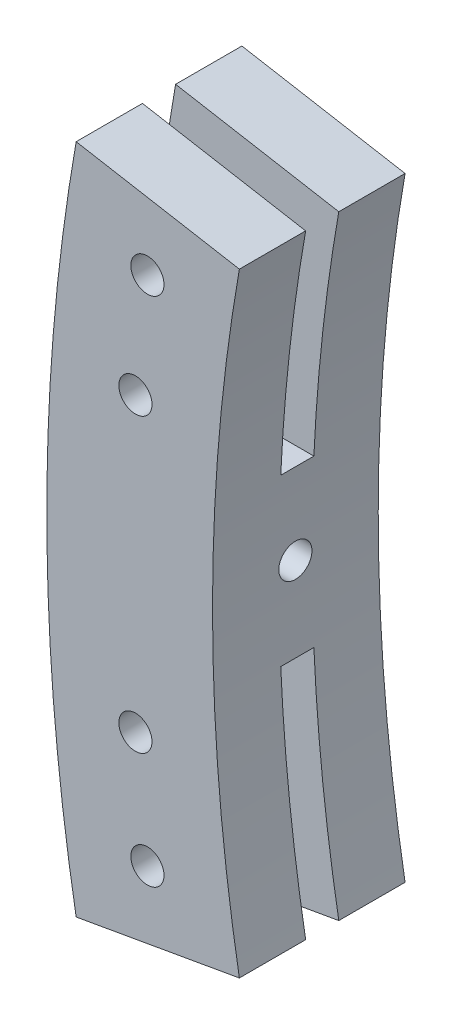
SolidWorks part; units mm, degrees
ref_plane "Front Plane" through (0, 0, 0) normal (0, 0, 1) x (1, 0, 0)
ref_plane "Top Plane" through (0, 0, 0) normal (0, 1, 0) x (1, 0, 0)
ref_plane "Right Plane" through (0, 0, 0) normal (1, 0, 0) x (0, 0, -1)
sketch "Sketch1" plane through (0, 0, 0) normal (0, 0, 1) x (1, 0, 0)
  line L0 (160, 0) -> (-167.5, 0) construction
  line L1 (0, 160) -> (0, -160) construction
  line L2 (0, 0) -> (-157.5692, 27.7837) construction
  line L3 (0, 0) -> (-157.5692, -27.7837) construction
  line L4 (-157.5692, 27.7837) -> (-172.3414, 30.3884)
  line L5 (-157.5692, -27.7837) -> (-172.3414, -30.3884)
  arc A0 (-157.5692, 27.7837) -> (-157.5692, -27.7837) centre (0, 0) ccw
  arc A1 (-172.3414, 30.3884) -> (-172.3414, -30.3884) centre (0, 0) ccw
  circle A2 centre (0, 0) radius 167.5 construction
  point P1 (-167.5, 0)
  point P20 (0, 0)
  dimension "D1" = 320
  dimension "D2" = 350
  dimension "D4" = 7.5
  dimension "D3" = 20
extrude "Boss-Extrude3" add sketch "Sketch1" along normal mid plane 15 contours L4 A1 A0 | A1 L5 A0 | A1 A0 region at (-166.7623, 0, 0)
extrude "Cut-Extrude4" cut sketch "Sketch1<6>" against normal mid plane 3
sketch "Sketch1<6>" plane through (0, 0, 0) normal (0, 0, 1) x (1, 0, 0) same geometry as "Sketch1"
sketch "Sketch6" plane through (0, 0, 0) normal (0, 0, 1) x (1, 0, 0)
  line L1 (-184.1488, 7.5) -> (-150.8512, 7.5)
  line L2 (-184.1488, 7.5) -> (-184.1488, -7.5)
  line L3 (-184.1488, -7.5) -> (-150.8512, -7.5)
  line L4 (-150.8512, 7.5) -> (-150.8512, -7.5)
  line L5 (-184.1488, 7.5) -> (-150.8512, -7.5) construction
  line L6 (-184.1488, -7.5) -> (-150.8512, 7.5) construction
  arc A0 (-172.3414, 30.3884) -> (-172.3414, -30.3884) centre (0, 0) ccw construction
  arc A1 (-157.5692, 27.7837) -> (-157.5692, -27.7837) centre (0, 0) ccw construction
  arc A2 (-172.3414, 30.3884) -> (-172.3414, -30.3884) centre (0, 0) ccw
  arc A3 (-157.5692, 27.7837) -> (-157.5692, -27.7837) centre (0, 0) ccw
  point P0 (-167.5, 0)
  dimension "D1" = 15
extrude "Boss-Extrude5" add sketch "Sketch6" along normal mid plane 3 contours A3 L1 A2 L3 region at (-167.4439, 0, 0)
ref_plane "Plane1" through (-167.5, 0, 0) normal (1, 0, 0) x (0, 0, -1)
sketch "Sketch4" plane through (-167.5, 0, 0) normal (1, 0, 0) x (0, 0, -1)
  circle A0 centre (0, 0) radius 3
  dimension "D1" = 6
extrude "bearing hole" cut sketch "Sketch4" against normal mid plane 2.5
sketch "Sketch7" plane through (-167.5, 0, 0) normal (1, 0, 0) x (0, 0, -1)
  circle A0 centre (0, 0) radius 1.5
  dimension "D1" = 3
extrude "shaft hole" cut sketch "Sketch7" against normal through all both and the other way through all
sketch "Sketch3" plane through (0, 0, 0) normal (0, 0, -1) x (-1, 0, 0)
  line L0 (0, 0) -> (157.5692, 27.7837) construction
  circle A0 centre (165.8913, 23.1586) radius 1.5
  circle A1 centre (0, 0) radius 167.5 construction
  circle A2 centre (166.9777, 13.2177) radius 1.5
  point P6 (0, 0)
  point P7 (166.0171, 22.2393)
  point P8 (167.1088, 11.441)
  point P9 (167.1073, 11.4628)
  point P12 (0, 0)
  dimension "D1" = 3
  dimension "D2" = 10
  dimension "D3" = 6
extrude "mount hole" cut sketch "Sketch3" against normal through all both and the other way through all
mirror "Mirror1" about plane through (0, 0, 0) normal (0, 1, 0) of "mount hole"
